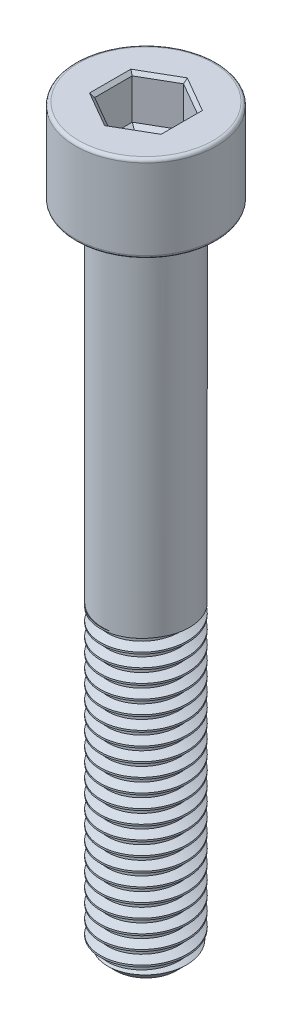
SolidWorks part; units mm, degrees
material "AISI Type A2 Tool Steel"
ref_plane "Front Plane" through (0, 0, 0) normal (0, 0, 1) x (1, 0, 0)
ref_plane "Top Plane" through (0, 0, 0) normal (0, 1, 0) x (1, 0, 0)
ref_plane "Right Plane" through (0, 0, 0) normal (1, 0, 0) x (0, 0, -1)
sketch "Sketch1" plane through (0, 0, 0) normal (0, 1, 0) x (1, 0, 0)
  circle A0 centre (0, 0) radius 4
  dimension "D1" = 8
extrude "Boss-Extrude1" add sketch "Sketch1" along normal blind 28
thread "Thread1" pitch 1.25 method cut profile "Thread Profile1" start angle 0, offset 2, length 0, pitch 1.25, diameter 8
ref_plane "Plane1" through (-4, 30, 0) normal (0, 0, 1) x (-1, 0, 0)
sketch "Thread Profile1" plane through (-4, 30, 0) normal (0, 0, 1) x (-1, 0, 0)
  line L0 (0, 0) -> (0, 1.25) construction
  line L11 (0, 0) -> (0, 1.0937)
  line L12 (0, 1.0937) -> (-0.6766, 0.7031)
  line L13 (-0.6766, 0.7031) -> (-0.6766, 0.3906)
  line L15 (-0.6766, 0.3906) -> (0, 0)
  line L17 (-0.6766, 0.5469) -> (0, 0.5469) construction
  point P2 (0, 0)
  dimension "Pitch" = 1.25
  dimension "Profile_Angle" = 60
  dimension "Profile_Land" = 0.3125
  dimension "Profile_Height" = 0.6766
sketch "Sketch2" plane through (0, 28, 0) normal (0, 1, 0) x (1, 0, 0)
  circle A0 centre (0, 0) radius 4
  dimension "D1" = 8
extrude "Boss-Extrude2" add sketch "Sketch2" along normal blind 32
sketch "Sketch5" plane through (0, 60, 0) normal (0, 1, 0) x (1, 0, 0)
  circle A0 centre (0, 0) radius 6.5
  dimension "D1" = 13
extrude "Boss-Extrude3" add sketch "Sketch5" along normal blind 8
sketch "Sketch6" plane through (0, 0, 0) normal (0, 0, 1) x (1, 0, 0)
  line L0 (0, 0) -> (0, 0.7245) construction
  line L1 (0, 0) -> (4.01, 0) construction
  line L2 (4.01, 0) -> (4.01, 1.2)
  line L3 (4.01, 1.2) -> (2.81, 0)
  line L4 (2.81, 0) -> (4.01, 0)
  dimension "D1" = 1.2
  dimension "D2" = 45
  dimension "D3" = 4.01
revolve "Cut-Revolve1" cut sketch "Sketch6" angle 360 about L0
fillet "Fillet1" radius 0.3 2 edges at (0, 60, 6.5) (0, 68, 6.5)
sketch "Sketch7" plane through (0, 68, 0) normal (0, 1, 0) x (1, 0, 0)
  line L1 (0, 3.4641) -> (-3, 1.7321)
  line L2 (-3, 1.7321) -> (-3, -1.7321)
  line L3 (-3, -1.7321) -> (0, -3.4641)
  line L4 (0, -3.4641) -> (3, -1.7321)
  line L5 (3, -1.7321) -> (3, 1.7321)
  line L6 (3, 1.7321) -> (0, 3.4641)
  circle A0 centre (0, 0) radius 3 construction
  dimension "D1" = 6
extrude "Cut-Extrude1" cut sketch "Sketch7" against normal blind 4
chamfer "Chamfer1" distance 0.3 angle 45 6 edges at (-3, 68, 0) (-1.5, 68, 2.5981) (1.5, 68, 2.5981) (3, 68, 0) (1.5, 68, -2.5981) (-1.5, 68, -2.5981)
sketch "Sketch8" plane through (0, 64, 0) normal (0, 1, 0) x (1, 0, 0)
  line L1 (0, 3.4641) -> (-3, 1.7321)
  line L2 (-3, 1.7321) -> (-3, -1.7321)
  line L3 (-3, -1.7321) -> (0, -3.4641)
  line L4 (0, -3.4641) -> (3, -1.7321)
  line L5 (3, -1.7321) -> (3, 1.7321)
  line L6 (3, 1.7321) -> (0, 3.4641)
  circle A0 centre (0, 0) radius 3 construction
extrude "Cut-Extrude2" cut sketch "Sketch8" against normal blind 0.4 draft 60
